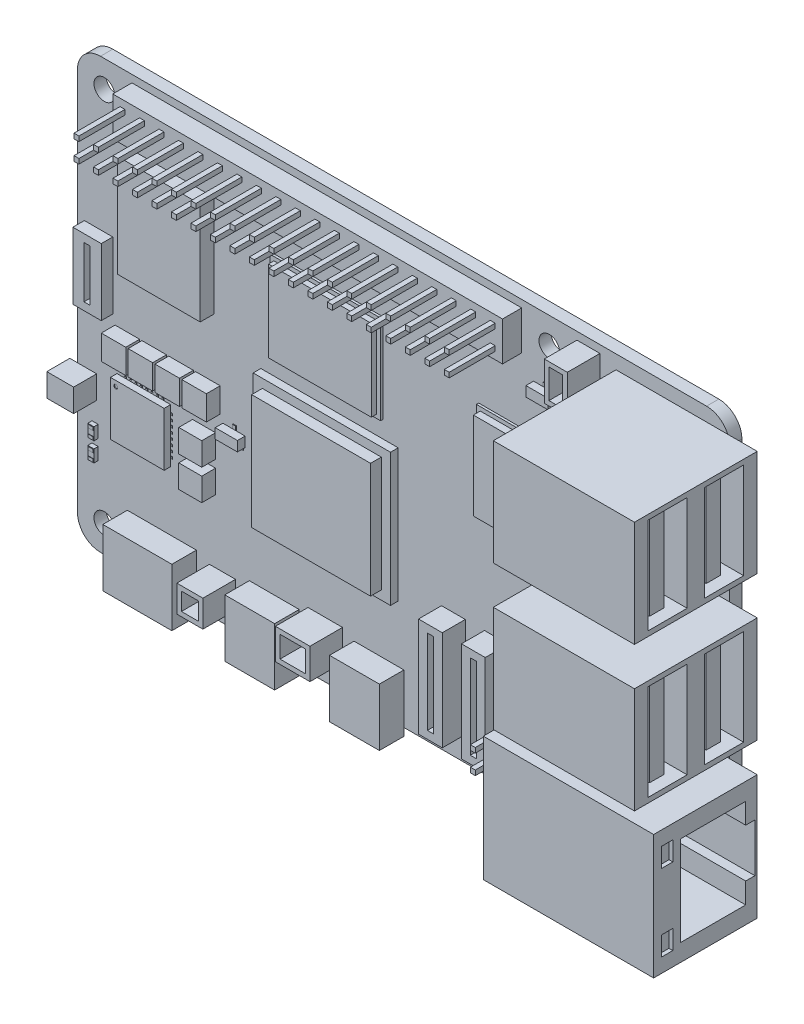
SolidWorks part; units mm, degrees
ref_plane "Front Plane" through (0, 0, 0) normal (0, 0, 1) x (1, 0, 0)
ref_plane "Top Plane" through (0, 0, 0) normal (0, 1, 0) x (1, 0, 0)
ref_plane "Right Plane" through (0, 0, 0) normal (1, 0, 0) x (0, 0, -1)
sketch "Sketch1" plane through (0, 0, 0) normal (0, 0, 1) x (1, 0, 0)
  line L0 (3, 0) -> (82, 0)
  line L1 (85, 3) -> (85, 53)
  line L2 (82, 56) -> (3, 56)
  line L3 (0, 53) -> (0, 3)
  arc A0 (82, 0) -> (85, 3) centre (82, 3) ccw
  arc A1 (85, 53) -> (82, 56) centre (82, 53) ccw
  arc A2 (3, 56) -> (0, 53) centre (3, 53) ccw
  arc A3 (0, 3) -> (3, 0) centre (3, 3) ccw
extrude "PCB" add sketch "Sketch1" along normal blind 1.6
ref_plane "Plane_z1_6" through (0, 0, 1.6) normal (0, 0, 1) x (1, 0, 0)
sketch "Sketch2" plane through (0, 0, 1.6) normal (0, 0, 1) x (1, 0, 0)
  line L1 (7.1, 49.96) -> (57.9, 49.96)
  line L2 (7.1, 49.96) -> (7.1, 55.04)
  line L3 (7.1, 55.04) -> (57.9, 55.04)
  line L4 (57.9, 49.96) -> (57.9, 55.04)
  line L6 (58.76, 6.76) -> (63.84, 6.76)
  line L7 (58.76, 6.76) -> (58.76, 11.84)
  line L8 (58.76, 11.84) -> (63.84, 11.84)
  line L9 (63.84, 6.76) -> (63.84, 11.84)
extrude "Header_Blocks" add sketch "Sketch2" along normal blind 2.5
ref_plane "Plane_z4_1" through (0, 0, 4.1) normal (0, 0, 1) x (1, 0, 0)
sketch "Sketch3" plane through (0, 0, 4.1) normal (0, 0, 1) x (1, 0, 0)
  line L1 (8.05, 50.91) -> (8.69, 50.91)
  line L2 (8.05, 50.91) -> (8.05, 51.55)
  line L3 (8.05, 51.55) -> (8.69, 51.55)
  line L4 (8.69, 50.91) -> (8.69, 51.55)
  line L6 (8.05, 53.45) -> (8.69, 53.45)
  line L7 (8.05, 53.45) -> (8.05, 54.09)
  line L8 (8.05, 54.09) -> (8.69, 54.09)
  line L9 (8.69, 53.45) -> (8.69, 54.09)
  line L11 (10.59, 50.91) -> (11.23, 50.91)
  line L12 (10.59, 50.91) -> (10.59, 51.55)
  line L13 (10.59, 51.55) -> (11.23, 51.55)
  line L14 (11.23, 50.91) -> (11.23, 51.55)
  line L16 (10.59, 53.45) -> (11.23, 53.45)
  line L17 (10.59, 53.45) -> (10.59, 54.09)
  line L18 (10.59, 54.09) -> (11.23, 54.09)
  line L19 (11.23, 53.45) -> (11.23, 54.09)
  line L21 (13.13, 50.91) -> (13.77, 50.91)
  line L22 (13.13, 50.91) -> (13.13, 51.55)
  line L23 (13.13, 51.55) -> (13.77, 51.55)
  line L24 (13.77, 50.91) -> (13.77, 51.55)
  line L26 (13.13, 53.45) -> (13.77, 53.45)
  line L27 (13.13, 53.45) -> (13.13, 54.09)
  line L28 (13.13, 54.09) -> (13.77, 54.09)
  line L29 (13.77, 53.45) -> (13.77, 54.09)
  line L31 (15.67, 50.91) -> (16.31, 50.91)
  line L32 (15.67, 50.91) -> (15.67, 51.55)
  line L33 (15.67, 51.55) -> (16.31, 51.55)
  line L34 (16.31, 50.91) -> (16.31, 51.55)
  line L36 (15.67, 53.45) -> (16.31, 53.45)
  line L37 (15.67, 53.45) -> (15.67, 54.09)
  line L38 (15.67, 54.09) -> (16.31, 54.09)
  line L39 (16.31, 53.45) -> (16.31, 54.09)
  line L41 (18.21, 50.91) -> (18.85, 50.91)
  line L42 (18.21, 50.91) -> (18.21, 51.55)
  line L43 (18.21, 51.55) -> (18.85, 51.55)
  line L44 (18.85, 50.91) -> (18.85, 51.55)
  line L46 (18.21, 53.45) -> (18.85, 53.45)
  line L47 (18.21, 53.45) -> (18.21, 54.09)
  line L48 (18.21, 54.09) -> (18.85, 54.09)
  line L49 (18.85, 53.45) -> (18.85, 54.09)
  line L51 (20.75, 50.91) -> (21.39, 50.91)
  line L52 (20.75, 50.91) -> (20.75, 51.55)
  line L53 (20.75, 51.55) -> (21.39, 51.55)
  line L54 (21.39, 50.91) -> (21.39, 51.55)
  line L56 (20.75, 53.45) -> (21.39, 53.45)
  line L57 (20.75, 53.45) -> (20.75, 54.09)
  line L58 (20.75, 54.09) -> (21.39, 54.09)
  line L59 (21.39, 53.45) -> (21.39, 54.09)
  line L61 (23.29, 50.91) -> (23.93, 50.91)
  line L62 (23.29, 50.91) -> (23.29, 51.55)
  line L63 (23.29, 51.55) -> (23.93, 51.55)
  line L64 (23.93, 50.91) -> (23.93, 51.55)
  line L66 (23.29, 53.45) -> (23.93, 53.45)
  line L67 (23.29, 53.45) -> (23.29, 54.09)
  line L68 (23.29, 54.09) -> (23.93, 54.09)
  line L69 (23.93, 53.45) -> (23.93, 54.09)
  line L71 (25.83, 50.91) -> (26.47, 50.91)
  line L72 (25.83, 50.91) -> (25.83, 51.55)
  line L73 (25.83, 51.55) -> (26.47, 51.55)
  line L74 (26.47, 50.91) -> (26.47, 51.55)
  line L76 (25.83, 53.45) -> (26.47, 53.45)
  line L77 (25.83, 53.45) -> (25.83, 54.09)
  line L78 (25.83, 54.09) -> (26.47, 54.09)
  line L79 (26.47, 53.45) -> (26.47, 54.09)
  line L81 (28.37, 50.91) -> (29.01, 50.91)
  line L82 (28.37, 50.91) -> (28.37, 51.55)
  line L83 (28.37, 51.55) -> (29.01, 51.55)
  line L84 (29.01, 50.91) -> (29.01, 51.55)
  line L86 (28.37, 53.45) -> (29.01, 53.45)
  line L87 (28.37, 53.45) -> (28.37, 54.09)
  line L88 (28.37, 54.09) -> (29.01, 54.09)
  line L89 (29.01, 53.45) -> (29.01, 54.09)
  line L91 (30.91, 50.91) -> (31.55, 50.91)
  line L92 (30.91, 50.91) -> (30.91, 51.55)
  line L93 (30.91, 51.55) -> (31.55, 51.55)
  line L94 (31.55, 50.91) -> (31.55, 51.55)
  line L96 (30.91, 53.45) -> (31.55, 53.45)
  line L97 (30.91, 53.45) -> (30.91, 54.09)
  line L98 (30.91, 54.09) -> (31.55, 54.09)
  line L99 (31.55, 53.45) -> (31.55, 54.09)
  line L101 (33.45, 50.91) -> (34.09, 50.91)
  line L102 (33.45, 50.91) -> (33.45, 51.55)
  line L103 (33.45, 51.55) -> (34.09, 51.55)
  line L104 (34.09, 50.91) -> (34.09, 51.55)
  line L106 (33.45, 53.45) -> (34.09, 53.45)
  line L107 (33.45, 53.45) -> (33.45, 54.09)
  line L108 (33.45, 54.09) -> (34.09, 54.09)
  line L109 (34.09, 53.45) -> (34.09, 54.09)
  line L111 (35.99, 50.91) -> (36.63, 50.91)
  line L112 (35.99, 50.91) -> (35.99, 51.55)
  line L113 (35.99, 51.55) -> (36.63, 51.55)
  line L114 (36.63, 50.91) -> (36.63, 51.55)
  line L116 (35.99, 53.45) -> (36.63, 53.45)
  line L117 (35.99, 53.45) -> (35.99, 54.09)
  line L118 (35.99, 54.09) -> (36.63, 54.09)
  line L119 (36.63, 53.45) -> (36.63, 54.09)
  line L121 (38.53, 50.91) -> (39.17, 50.91)
  line L122 (38.53, 50.91) -> (38.53, 51.55)
  line L123 (38.53, 51.55) -> (39.17, 51.55)
  line L124 (39.17, 50.91) -> (39.17, 51.55)
  line L126 (38.53, 53.45) -> (39.17, 53.45)
  line L127 (38.53, 53.45) -> (38.53, 54.09)
  line L128 (38.53, 54.09) -> (39.17, 54.09)
  line L129 (39.17, 53.45) -> (39.17, 54.09)
  line L131 (41.07, 50.91) -> (41.71, 50.91)
  line L132 (41.07, 50.91) -> (41.07, 51.55)
  line L133 (41.07, 51.55) -> (41.71, 51.55)
  line L134 (41.71, 50.91) -> (41.71, 51.55)
  line L136 (41.07, 53.45) -> (41.71, 53.45)
  line L137 (41.07, 53.45) -> (41.07, 54.09)
  line L138 (41.07, 54.09) -> (41.71, 54.09)
  line L139 (41.71, 53.45) -> (41.71, 54.09)
  line L141 (43.61, 50.91) -> (44.25, 50.91)
  line L142 (43.61, 50.91) -> (43.61, 51.55)
  line L143 (43.61, 51.55) -> (44.25, 51.55)
  line L144 (44.25, 50.91) -> (44.25, 51.55)
  line L146 (43.61, 53.45) -> (44.25, 53.45)
  line L147 (43.61, 53.45) -> (43.61, 54.09)
  line L148 (43.61, 54.09) -> (44.25, 54.09)
  line L149 (44.25, 53.45) -> (44.25, 54.09)
  line L151 (46.15, 50.91) -> (46.79, 50.91)
  line L152 (46.15, 50.91) -> (46.15, 51.55)
  line L153 (46.15, 51.55) -> (46.79, 51.55)
  line L154 (46.79, 50.91) -> (46.79, 51.55)
  line L156 (46.15, 53.45) -> (46.79, 53.45)
  line L157 (46.15, 53.45) -> (46.15, 54.09)
  line L158 (46.15, 54.09) -> (46.79, 54.09)
  line L159 (46.79, 53.45) -> (46.79, 54.09)
  line L161 (48.69, 50.91) -> (49.33, 50.91)
  line L162 (48.69, 50.91) -> (48.69, 51.55)
  line L163 (48.69, 51.55) -> (49.33, 51.55)
  line L164 (49.33, 50.91) -> (49.33, 51.55)
  line L166 (48.69, 53.45) -> (49.33, 53.45)
  line L167 (48.69, 53.45) -> (48.69, 54.09)
  line L168 (48.69, 54.09) -> (49.33, 54.09)
  line L169 (49.33, 53.45) -> (49.33, 54.09)
  line L171 (51.23, 50.91) -> (51.87, 50.91)
  line L172 (51.23, 50.91) -> (51.23, 51.55)
  line L173 (51.23, 51.55) -> (51.87, 51.55)
  line L174 (51.87, 50.91) -> (51.87, 51.55)
  line L176 (51.23, 53.45) -> (51.87, 53.45)
  line L177 (51.23, 53.45) -> (51.23, 54.09)
  line L178 (51.23, 54.09) -> (51.87, 54.09)
  line L179 (51.87, 53.45) -> (51.87, 54.09)
  line L181 (53.77, 50.91) -> (54.41, 50.91)
  line L182 (53.77, 50.91) -> (53.77, 51.55)
  line L183 (53.77, 51.55) -> (54.41, 51.55)
  line L184 (54.41, 50.91) -> (54.41, 51.55)
  line L186 (53.77, 53.45) -> (54.41, 53.45)
  line L187 (53.77, 53.45) -> (53.77, 54.09)
  line L188 (53.77, 54.09) -> (54.41, 54.09)
  line L189 (54.41, 53.45) -> (54.41, 54.09)
  line L191 (56.31, 50.91) -> (56.95, 50.91)
  line L192 (56.31, 50.91) -> (56.31, 51.55)
  line L193 (56.31, 51.55) -> (56.95, 51.55)
  line L194 (56.95, 50.91) -> (56.95, 51.55)
  line L196 (56.31, 53.45) -> (56.95, 53.45)
  line L197 (56.31, 53.45) -> (56.31, 54.09)
  line L198 (56.31, 54.09) -> (56.95, 54.09)
  line L199 (56.95, 53.45) -> (56.95, 54.09)
  line L201 (59.71, 7.71) -> (60.35, 7.71)
  line L202 (59.71, 7.71) -> (59.71, 8.35)
  line L203 (59.71, 8.35) -> (60.35, 8.35)
  line L204 (60.35, 7.71) -> (60.35, 8.35)
  line L206 (59.71, 10.25) -> (60.35, 10.25)
  line L207 (59.71, 10.25) -> (59.71, 10.89)
  line L208 (59.71, 10.89) -> (60.35, 10.89)
  line L209 (60.35, 10.25) -> (60.35, 10.89)
  line L211 (62.25, 7.71) -> (62.89, 7.71)
  line L212 (62.25, 7.71) -> (62.25, 8.35)
  line L213 (62.25, 8.35) -> (62.89, 8.35)
  line L214 (62.89, 7.71) -> (62.89, 8.35)
  line L216 (62.25, 10.25) -> (62.89, 10.25)
  line L217 (62.25, 10.25) -> (62.25, 10.89)
  line L218 (62.25, 10.89) -> (62.89, 10.89)
  line L219 (62.89, 10.25) -> (62.89, 10.89)
extrude "Header_Pins" add sketch "Sketch3" along normal blind 6
sketch "Sketch4" plane through (0, 0, 1.6) normal (0, 0, 1) x (1, 0, 0)
  line L1 (6.125, 14.1) -> (6.375, 14.1)
  line L2 (6.125, 14.1) -> (6.125, 14.4)
  line L3 (6.125, 14.4) -> (6.375, 14.4)
  line L4 (6.375, 14.1) -> (6.375, 14.4)
  line L6 (5, 15.225) -> (5.3, 15.225)
  line L7 (5, 15.225) -> (5, 15.475)
  line L8 (5, 15.475) -> (5.3, 15.475)
  line L9 (5.3, 15.225) -> (5.3, 15.475)
  line L11 (6.125, 21.2) -> (6.375, 21.2)
  line L12 (6.125, 21.2) -> (6.125, 21.5)
  line L13 (6.125, 21.5) -> (6.375, 21.5)
  line L14 (6.375, 21.2) -> (6.375, 21.5)
  line L16 (12.1, 15.225) -> (12.4, 15.225)
  line L17 (12.1, 15.225) -> (12.1, 15.475)
  line L18 (12.1, 15.475) -> (12.4, 15.475)
  line L19 (12.4, 15.225) -> (12.4, 15.475)
  line L21 (6.825, 14.1) -> (7.075, 14.1)
  line L22 (6.825, 14.1) -> (6.825, 14.4)
  line L23 (6.825, 14.4) -> (7.075, 14.4)
  line L24 (7.075, 14.1) -> (7.075, 14.4)
  line L26 (5, 15.925) -> (5.3, 15.925)
  line L27 (5, 15.925) -> (5, 16.175)
  line L28 (5, 16.175) -> (5.3, 16.175)
  line L29 (5.3, 15.925) -> (5.3, 16.175)
  line L31 (6.825, 21.2) -> (7.075, 21.2)
  line L32 (6.825, 21.2) -> (6.825, 21.5)
  line L33 (6.825, 21.5) -> (7.075, 21.5)
  line L34 (7.075, 21.2) -> (7.075, 21.5)
  line L36 (12.1, 15.925) -> (12.4, 15.925)
  line L37 (12.1, 15.925) -> (12.1, 16.175)
  line L38 (12.1, 16.175) -> (12.4, 16.175)
  line L39 (12.4, 15.925) -> (12.4, 16.175)
  line L41 (7.525, 14.1) -> (7.775, 14.1)
  line L42 (7.525, 14.1) -> (7.525, 14.4)
  line L43 (7.525, 14.4) -> (7.775, 14.4)
  line L44 (7.775, 14.1) -> (7.775, 14.4)
  line L46 (5, 16.625) -> (5.3, 16.625)
  line L47 (5, 16.625) -> (5, 16.875)
  line L48 (5, 16.875) -> (5.3, 16.875)
  line L49 (5.3, 16.625) -> (5.3, 16.875)
  line L51 (7.525, 21.2) -> (7.775, 21.2)
  line L52 (7.525, 21.2) -> (7.525, 21.5)
  line L53 (7.525, 21.5) -> (7.775, 21.5)
  line L54 (7.775, 21.2) -> (7.775, 21.5)
  line L56 (12.1, 16.625) -> (12.4, 16.625)
  line L57 (12.1, 16.625) -> (12.1, 16.875)
  line L58 (12.1, 16.875) -> (12.4, 16.875)
  line L59 (12.4, 16.625) -> (12.4, 16.875)
  line L61 (8.225, 14.1) -> (8.475, 14.1)
  line L62 (8.225, 14.1) -> (8.225, 14.4)
  line L63 (8.225, 14.4) -> (8.475, 14.4)
  line L64 (8.475, 14.1) -> (8.475, 14.4)
  line L66 (5, 17.325) -> (5.3, 17.325)
  line L67 (5, 17.325) -> (5, 17.575)
  line L68 (5, 17.575) -> (5.3, 17.575)
  line L69 (5.3, 17.325) -> (5.3, 17.575)
  line L71 (8.225, 21.2) -> (8.475, 21.2)
  line L72 (8.225, 21.2) -> (8.225, 21.5)
  line L73 (8.225, 21.5) -> (8.475, 21.5)
  line L74 (8.475, 21.2) -> (8.475, 21.5)
  line L76 (12.1, 17.325) -> (12.4, 17.325)
  line L77 (12.1, 17.325) -> (12.1, 17.575)
  line L78 (12.1, 17.575) -> (12.4, 17.575)
  line L79 (12.4, 17.325) -> (12.4, 17.575)
  line L81 (8.925, 14.1) -> (9.175, 14.1)
  line L82 (8.925, 14.1) -> (8.925, 14.4)
  line L83 (8.925, 14.4) -> (9.175, 14.4)
  line L84 (9.175, 14.1) -> (9.175, 14.4)
  line L86 (5, 18.025) -> (5.3, 18.025)
  line L87 (5, 18.025) -> (5, 18.275)
  line L88 (5, 18.275) -> (5.3, 18.275)
  line L89 (5.3, 18.025) -> (5.3, 18.275)
  line L91 (8.925, 21.2) -> (9.175, 21.2)
  line L92 (8.925, 21.2) -> (8.925, 21.5)
  line L93 (8.925, 21.5) -> (9.175, 21.5)
  line L94 (9.175, 21.2) -> (9.175, 21.5)
  line L96 (12.1, 18.025) -> (12.4, 18.025)
  line L97 (12.1, 18.025) -> (12.1, 18.275)
  line L98 (12.1, 18.275) -> (12.4, 18.275)
  line L99 (12.4, 18.025) -> (12.4, 18.275)
  line L101 (9.625, 14.1) -> (9.875, 14.1)
  line L102 (9.625, 14.1) -> (9.625, 14.4)
  line L103 (9.625, 14.4) -> (9.875, 14.4)
  line L104 (9.875, 14.1) -> (9.875, 14.4)
  line L106 (5, 18.725) -> (5.3, 18.725)
  line L107 (5, 18.725) -> (5, 18.975)
  line L108 (5, 18.975) -> (5.3, 18.975)
  line L109 (5.3, 18.725) -> (5.3, 18.975)
  line L111 (9.625, 21.2) -> (9.875, 21.2)
  line L112 (9.625, 21.2) -> (9.625, 21.5)
  line L113 (9.625, 21.5) -> (9.875, 21.5)
  line L114 (9.875, 21.2) -> (9.875, 21.5)
  line L116 (12.1, 18.725) -> (12.4, 18.725)
  line L117 (12.1, 18.725) -> (12.1, 18.975)
  line L118 (12.1, 18.975) -> (12.4, 18.975)
  line L119 (12.4, 18.725) -> (12.4, 18.975)
  line L121 (10.325, 14.1) -> (10.575, 14.1)
  line L122 (10.325, 14.1) -> (10.325, 14.35)
  line L123 (10.325, 14.35) -> (10.575, 14.35)
  line L124 (10.575, 14.1) -> (10.575, 14.35)
  line L126 (5, 19.425) -> (5.25, 19.425)
  line L127 (5, 19.425) -> (5, 19.675)
  line L128 (5, 19.675) -> (5.25, 19.675)
  line L129 (5.25, 19.425) -> (5.25, 19.675)
  line L131 (10.325, 21.2) -> (10.575, 21.2)
  line L132 (10.325, 21.2) -> (10.325, 21.5)
  line L133 (10.325, 21.5) -> (10.575, 21.5)
  line L134 (10.575, 21.2) -> (10.575, 21.5)
  line L136 (12.1, 19.425) -> (12.4, 19.425)
  line L137 (12.1, 19.425) -> (12.1, 19.675)
  line L138 (12.1, 19.675) -> (12.4, 19.675)
  line L139 (12.4, 19.425) -> (12.4, 19.675)
  line L141 (11.025, 14.1) -> (11.275, 14.1)
  line L142 (11.025, 14.1) -> (11.025, 14.4)
  line L143 (11.025, 14.4) -> (11.275, 14.4)
  line L144 (11.275, 14.1) -> (11.275, 14.4)
  line L146 (5, 20.125) -> (5.3, 20.125)
  line L147 (5, 20.125) -> (5, 20.375)
  line L148 (5, 20.375) -> (5.3, 20.375)
  line L149 (5.3, 20.125) -> (5.3, 20.375)
  line L151 (11.025, 21.2) -> (11.275, 21.2)
  line L152 (11.025, 21.2) -> (11.025, 21.5)
  line L153 (11.025, 21.5) -> (11.275, 21.5)
  line L154 (11.275, 21.2) -> (11.275, 21.5)
  line L156 (12.1, 20.125) -> (12.4, 20.125)
  line L157 (12.1, 20.125) -> (12.1, 20.375)
  line L158 (12.1, 20.375) -> (12.4, 20.375)
  line L159 (12.4, 20.125) -> (12.4, 20.375)
  line L161 (66.275, 43.15) -> (66.525, 43.15)
  line L162 (66.275, 43.15) -> (66.275, 43.45)
  line L163 (66.275, 43.45) -> (66.525, 43.45)
  line L164 (66.525, 43.15) -> (66.525, 43.45)
  line L166 (65.2, 44.475) -> (65.5, 44.475)
  line L167 (65.2, 44.475) -> (65.2, 44.725)
  line L168 (65.2, 44.725) -> (65.5, 44.725)
  line L169 (65.5, 44.475) -> (65.5, 44.725)
  line L171 (66.275, 47.75) -> (66.525, 47.75)
  line L172 (66.275, 47.75) -> (66.275, 48.05)
  line L173 (66.275, 48.05) -> (66.525, 48.05)
  line L174 (66.525, 47.75) -> (66.525, 48.05)
  line L176 (69.3, 44.475) -> (69.6, 44.475)
  line L177 (69.3, 44.475) -> (69.3, 44.725)
  line L178 (69.3, 44.725) -> (69.6, 44.725)
  line L179 (69.6, 44.475) -> (69.6, 44.725)
  line L181 (66.9417, 43.15) -> (67.1917, 43.15)
  line L182 (66.9417, 43.15) -> (66.9417, 43.45)
  line L183 (66.9417, 43.45) -> (67.1917, 43.45)
  line L184 (67.1917, 43.15) -> (67.1917, 43.45)
  line L186 (65.2, 45.1417) -> (65.5, 45.1417)
  line L187 (65.2, 45.1417) -> (65.2, 45.3917)
  line L188 (65.2, 45.3917) -> (65.5, 45.3917)
  line L189 (65.5, 45.1417) -> (65.5, 45.3917)
  line L191 (66.9417, 47.75) -> (67.1917, 47.75)
  line L192 (66.9417, 47.75) -> (66.9417, 48.05)
  line L193 (66.9417, 48.05) -> (67.1917, 48.05)
  line L194 (67.1917, 47.75) -> (67.1917, 48.05)
  line L196 (69.3, 45.1417) -> (69.6, 45.1417)
  line L197 (69.3, 45.1417) -> (69.3, 45.3917)
  line L198 (69.3, 45.3917) -> (69.6, 45.3917)
  line L199 (69.6, 45.1417) -> (69.6, 45.3917)
  line L201 (67.6083, 43.15) -> (67.8583, 43.15)
  line L202 (67.6083, 43.15) -> (67.6083, 43.45)
  line L203 (67.6083, 43.45) -> (67.8583, 43.45)
  line L204 (67.8583, 43.15) -> (67.8583, 43.45)
  line L206 (65.2, 45.8083) -> (65.5, 45.8083)
  line L207 (65.2, 45.8083) -> (65.2, 46.0583)
  line L208 (65.2, 46.0583) -> (65.5, 46.0583)
  line L209 (65.5, 45.8083) -> (65.5, 46.0583)
  line L211 (67.6083, 47.75) -> (67.8583, 47.75)
  line L212 (67.6083, 47.75) -> (67.6083, 48.05)
  line L213 (67.6083, 48.05) -> (67.8583, 48.05)
  line L214 (67.8583, 47.75) -> (67.8583, 48.05)
  line L216 (69.3, 45.8083) -> (69.6, 45.8083)
  line L217 (69.3, 45.8083) -> (69.3, 46.0583)
  line L218 (69.3, 46.0583) -> (69.6, 46.0583)
  line L219 (69.6, 45.8083) -> (69.6, 46.0583)
  line L221 (68.275, 43.15) -> (68.525, 43.15)
  line L222 (68.275, 43.15) -> (68.275, 43.45)
  line L223 (68.275, 43.45) -> (68.525, 43.45)
  line L224 (68.525, 43.15) -> (68.525, 43.45)
  line L226 (65.2, 46.475) -> (65.5, 46.475)
  line L227 (65.2, 46.475) -> (65.2, 46.725)
  line L228 (65.2, 46.725) -> (65.5, 46.725)
  line L229 (65.5, 46.475) -> (65.5, 46.725)
  line L231 (68.275, 47.75) -> (68.525, 47.75)
  line L232 (68.275, 47.75) -> (68.275, 48.05)
  line L233 (68.275, 48.05) -> (68.525, 48.05)
  line L234 (68.525, 47.75) -> (68.525, 48.05)
  line L236 (69.3, 46.475) -> (69.6, 46.475)
  line L237 (69.3, 46.475) -> (69.3, 46.725)
  line L238 (69.3, 46.725) -> (69.6, 46.725)
  line L239 (69.6, 46.475) -> (69.6, 46.725)
extrude "Parts_add00" add sketch "Sketch4" along normal blind 0.05
sketch "Sketch5" plane through (0, 0, 1.6) normal (0, 0, 1) x (1, 0, 0)
  line L1 (19.35, 20.85) -> (19.75, 20.85)
  line L2 (19.35, 20.85) -> (19.35, 21.55)
  line L3 (19.35, 21.55) -> (19.75, 21.55)
  line L4 (19.75, 20.85) -> (19.75, 21.55)
  line L6 (21.25, 20.85) -> (21.65, 20.85)
  line L7 (21.25, 20.85) -> (21.25, 21.55)
  line L8 (21.25, 21.55) -> (21.65, 21.55)
  line L9 (21.65, 20.85) -> (21.65, 21.55)
  line L11 (20.3, 22.45) -> (20.7, 22.45)
  line L12 (20.3, 22.45) -> (20.3, 23.15)
  line L13 (20.3, 23.15) -> (20.7, 23.15)
  line L14 (20.7, 22.45) -> (20.7, 23.15)
  line L16 (58.35, 16.85) -> (58.75, 16.85)
  line L17 (58.35, 16.85) -> (58.35, 17.55)
  line L18 (58.35, 17.55) -> (58.75, 17.55)
  line L19 (58.75, 16.85) -> (58.75, 17.55)
  line L21 (60.25, 16.85) -> (60.65, 16.85)
  line L22 (60.25, 16.85) -> (60.25, 17.55)
  line L23 (60.25, 17.55) -> (60.65, 17.55)
  line L24 (60.65, 16.85) -> (60.65, 17.55)
  line L26 (59.3, 18.45) -> (59.7, 18.45)
  line L27 (59.3, 18.45) -> (59.3, 19.15)
  line L28 (59.3, 19.15) -> (59.7, 19.15)
  line L29 (59.7, 18.45) -> (59.7, 19.15)
  line L31 (59.85, 45.85) -> (60.25, 45.85)
  line L32 (59.85, 45.85) -> (59.85, 46.55)
  line L33 (59.85, 46.55) -> (60.25, 46.55)
  line L34 (60.25, 45.85) -> (60.25, 46.55)
  line L36 (61.75, 45.85) -> (62.15, 45.85)
  line L37 (61.75, 45.85) -> (61.75, 46.55)
  line L38 (61.75, 46.55) -> (62.15, 46.55)
  line L39 (62.15, 45.85) -> (62.15, 46.55)
  line L41 (60.8, 47.45) -> (61.2, 47.45)
  line L42 (60.8, 47.45) -> (60.8, 48.15)
  line L43 (60.8, 48.15) -> (61.2, 48.15)
  line L44 (61.2, 47.45) -> (61.2, 48.15)
extrude "Parts_add01" add sketch "Sketch5" along normal blind 0.1
sketch "Sketch6" plane through (0, 0, 1.6) normal (0, 0, 1) x (1, 0, 0)
  line L1 (25.4, 33.4) -> (39.8, 33.4)
  line L2 (25.4, 33.4) -> (25.4, 45)
  line L3 (25.4, 45) -> (39.8, 45)
  line L4 (39.8, 33.4) -> (39.8, 45)
  line L6 (52.3, 29.1) -> (65.2, 29.1)
  line L7 (52.3, 29.1) -> (52.3, 41.5)
  line L8 (52.3, 41.5) -> (65.2, 41.5)
  line L9 (65.2, 29.1) -> (65.2, 41.5)
extrude "Parts_add02" add sketch "Sketch6" along normal blind 0.3
sketch "Sketch7" plane through (0, 0, 1.6) normal (0, 0, 1) x (1, 0, 0)
  line L1 (1.9, 10.2) -> (2.7, 10.2)
  line L2 (1.9, 10.2) -> (1.9, 11.8)
  line L3 (1.9, 11.8) -> (2.7, 11.8)
  line L4 (2.7, 10.2) -> (2.7, 11.8)
  line L6 (1.9, 12.7) -> (2.7, 12.7)
  line L7 (1.9, 12.7) -> (1.9, 14.3)
  line L8 (1.9, 14.3) -> (2.7, 14.3)
  line L9 (2.7, 12.7) -> (2.7, 14.3)
extrude "Parts_add03" add sketch "Sketch7" along normal blind 0.55
sketch "Sketch8" plane through (0, 0, 1.6) normal (0, 0, 1) x (1, 0, 0)
  line L0 (62.7, 19.918) -> (65.882, 23.1)
  line L1 (65.882, 23.1) -> (62.7, 26.282)
  line L2 (62.7, 26.282) -> (59.518, 23.1)
  line L3 (59.518, 23.1) -> (62.7, 19.918)
extrude "Parts_add04" add sketch "Sketch8" along normal blind 0.9
sketch "Sketch9" plane through (0, 0, 1.6) normal (0, 0, 1) x (1, 0, 0)
  line L1 (23.9, 13.9) -> (41.8, 13.9)
  line L2 (23.9, 13.9) -> (23.9, 31.2)
  line L3 (23.9, 31.2) -> (41.8, 31.2)
  line L4 (41.8, 13.9) -> (41.8, 31.2)
extrude "Parts_add05" add sketch "Sketch9" along normal blind 1
sketch "Sketch10" plane through (0, 0, 1.6) normal (0, 0, 1) x (1, 0, 0)
  line L1 (0.9, 27.7) -> (4.6, 27.7)
  line L2 (0.9, 27.7) -> (0.9, 36.4)
  line L3 (0.9, 36.4) -> (4.6, 36.4)
  line L4 (4.6, 27.7) -> (4.6, 36.4)
extrude "Parts_add06" add sketch "Sketch10" along normal blind 1.5
sketch "Sketch11" plane through (0, 0, 1.6) normal (0, 0, 1) x (1, 0, 0)
  line L1 (7, 34.3) -> (17.8, 34.3)
  line L2 (7, 34.3) -> (7, 47.6)
  line L3 (7, 47.6) -> (17.8, 47.6)
  line L4 (17.8, 34.3) -> (17.8, 47.6)
  line L6 (4.9, 23.4) -> (8.1, 23.4)
  line L7 (4.9, 23.4) -> (4.9, 26.6)
  line L8 (4.9, 26.6) -> (8.1, 26.6)
  line L9 (8.1, 23.4) -> (8.1, 26.6)
  line L11 (8.4, 23.4) -> (11.6, 23.4)
  line L12 (8.4, 23.4) -> (8.4, 26.6)
  line L13 (8.4, 26.6) -> (11.6, 26.6)
  line L14 (11.6, 23.4) -> (11.6, 26.6)
  line L16 (11.9, 23.4) -> (15.1, 23.4)
  line L17 (11.9, 23.4) -> (11.9, 26.6)
  line L18 (11.9, 26.6) -> (15.1, 26.6)
  line L19 (15.1, 23.4) -> (15.1, 26.6)
  line L21 (15.4, 23.4) -> (18.6, 23.4)
  line L22 (15.4, 23.4) -> (15.4, 26.6)
  line L23 (15.4, 26.6) -> (18.6, 26.6)
  line L24 (18.6, 23.4) -> (18.6, 26.6)
  line L26 (15, 18) -> (18, 18)
  line L27 (15, 18) -> (15, 21)
  line L28 (15, 21) -> (18, 21)
  line L29 (18, 18) -> (18, 21)
  line L31 (15, 14) -> (18, 14)
  line L32 (15, 14) -> (15, 17)
  line L33 (15, 17) -> (18, 17)
  line L34 (18, 14) -> (18, 17)
extrude "Parts_add07" add sketch "Sketch11" along normal blind 1.8
sketch "Sketch12" plane through (0, 0, 1.6) normal (0, 0, 1) x (1, 0, 0)
  line L1 (53.05, 3.2) -> (56.15, 3.2)
  line L2 (53.05, 3.2) -> (53.05, 16.2)
  line L3 (53.05, 16.2) -> (56.15, 16.2)
  line L4 (56.15, 3.2) -> (56.15, 16.2)
  line L6 (47.45, 3.2) -> (50.55, 3.2)
  line L7 (47.45, 3.2) -> (47.45, 16.2)
  line L8 (47.45, 16.2) -> (50.55, 16.2)
  line L9 (50.55, 3.2) -> (50.55, 16.2)
  line L11 (-1, 16.9) -> (2.5, 16.9)
  line L12 (-1, 16.9) -> (-1, 19.9)
  line L13 (-1, 19.9) -> (2.5, 19.9)
  line L14 (2.5, 16.9) -> (2.5, 19.9)
extrude "Parts_add08" add sketch "Sketch12" along normal blind 3
sketch "Sketch13" plane through (0, 0, 1.6) normal (0, 0, 1) x (1, 0, 0)
  line L1 (22.4, -1) -> (28.9, -1)
  line L2 (22.4, -1) -> (22.4, 6.5)
  line L3 (22.4, 6.5) -> (28.9, 6.5)
  line L4 (28.9, -1) -> (28.9, 6.5)
  line L6 (36.05, -1) -> (42.55, -1)
  line L7 (36.05, -1) -> (36.05, 6.5)
  line L8 (36.05, 6.5) -> (42.55, 6.5)
  line L9 (42.55, -1) -> (42.55, 6.5)
  line L11 (6.5, -1) -> (15.5, -1)
  line L12 (6.5, -1) -> (6.5, 6.5)
  line L13 (6.5, 6.5) -> (15.5, 6.5)
  line L14 (15.5, -1) -> (15.5, 6.5)
extrude "Parts_add09" add sketch "Sketch13" along normal blind 3.2
sketch "Sketch14" plane through (0, 0, 1.6) normal (0, 0, 1) x (1, 0, 0)
  line L1 (65.1, 50) -> (68.1, 50)
  line L2 (65.1, 50) -> (65.1, 55)
  line L3 (65.1, 55) -> (68.1, 55)
  line L4 (68.1, 50) -> (68.1, 55)
  line L6 (30.05, 3.3) -> (34.55, 3.3)
  line L7 (30.05, 3.3) -> (30.05, 7.3)
  line L8 (30.05, 7.3) -> (34.55, 7.3)
  line L9 (34.55, 3.3) -> (34.55, 7.3)
  line L11 (17.2, 2.25) -> (20.6, 2.25)
  line L12 (17.2, 2.25) -> (17.2, 5.75)
  line L13 (17.2, 5.75) -> (20.6, 5.75)
  line L14 (20.6, 2.25) -> (20.6, 5.75)
extrude "Parts_add10" add sketch "Sketch14" along normal blind 4.25
sketch "Sketch15" plane through (0, 0, 1.6) normal (0, 0, 1) x (1, 0, 0)
  line L1 (66.4, 1.5) -> (88.6, 1.5)
  line L2 (66.4, 1.5) -> (66.4, 17.7)
  line L3 (66.4, 17.7) -> (88.6, 17.7)
  line L4 (88.6, 1.5) -> (88.6, 17.7)
extrude "Parts_add11" add sketch "Sketch15" along normal blind 13.5
sketch "Sketch16" plane through (0, 0, 1.6) normal (0, 0, 1) x (1, 0, 0)
  line L1 (70.2, 40.4) -> (88.6, 40.4)
  line L2 (70.2, 40.4) -> (70.2, 54.2)
  line L3 (70.2, 54.2) -> (88.6, 54.2)
  line L4 (88.6, 40.4) -> (88.6, 54.2)
  line L6 (70.2, 21.6) -> (88.6, 21.6)
  line L7 (70.2, 21.6) -> (70.2, 35.4)
  line L8 (70.2, 35.4) -> (88.6, 35.4)
  line L9 (88.6, 21.6) -> (88.6, 35.4)
extrude "Parts_add12" add sketch "Sketch16" along normal blind 16
ref_plane "Plane_z1_65" through (0, 0, 1.65) normal (0, 0, 1) x (1, 0, 0)
sketch "Sketch17" plane through (0, 0, 1.65) normal (0, 0, 1) x (1, 0, 0)
  line L1 (5.2, 14.3) -> (12.2, 14.3)
  line L2 (5.2, 14.3) -> (5.2, 21.3)
  line L3 (5.2, 21.3) -> (12.2, 21.3)
  line L4 (12.2, 14.3) -> (12.2, 21.3)
extrude "Parts_add13" add sketch "Sketch17" along normal blind 0.85
sketch "Sketch18" plane through (0, 0, 1.65) normal (0, 0, 1) x (1, 0, 0)
  line L1 (65.4, 43.35) -> (69.4, 43.35)
  line L2 (65.4, 43.35) -> (65.4, 47.85)
  line L3 (65.4, 47.85) -> (69.4, 47.85)
  line L4 (69.4, 43.35) -> (69.4, 47.85)
extrude "Parts_add14" add sketch "Sketch18" along normal blind 0.95
ref_plane "Plane_z1_7" through (0, 0, 1.7) normal (0, 0, 1) x (1, 0, 0)
sketch "Sketch19" plane through (0, 0, 1.7) normal (0, 0, 1) x (1, 0, 0)
  line L1 (19.05, 21.35) -> (21.95, 21.35)
  line L2 (19.05, 21.35) -> (19.05, 22.65)
  line L3 (19.05, 22.65) -> (21.95, 22.65)
  line L4 (21.95, 21.35) -> (21.95, 22.65)
  line L6 (58.05, 17.35) -> (60.95, 17.35)
  line L7 (58.05, 17.35) -> (58.05, 18.65)
  line L8 (58.05, 18.65) -> (60.95, 18.65)
  line L9 (60.95, 17.35) -> (60.95, 18.65)
  line L11 (59.55, 46.35) -> (62.45, 46.35)
  line L12 (59.55, 46.35) -> (59.55, 47.65)
  line L13 (59.55, 47.65) -> (62.45, 47.65)
  line L14 (62.45, 46.35) -> (62.45, 47.65)
extrude "Parts_add15" add sketch "Sketch19" along normal blind 1
ref_plane "Plane_z1_9" through (0, 0, 1.9) normal (0, 0, 1) x (1, 0, 0)
sketch "Sketch20" plane through (0, 0, 1.9) normal (0, 0, 1) x (1, 0, 0)
  line L1 (25.9, 33.9) -> (39.3, 33.9)
  line L2 (25.9, 33.9) -> (25.9, 44.5)
  line L3 (25.9, 44.5) -> (39.3, 44.5)
  line L4 (39.3, 33.9) -> (39.3, 44.5)
extrude "Parts_add16" add sketch "Sketch20" along normal blind 0.7
sketch "Sketch21" plane through (0, 0, 1.9) normal (0, 0, 1) x (1, 0, 0)
  line L1 (52.8, 29.6) -> (64.7, 29.6)
  line L2 (52.8, 29.6) -> (52.8, 41)
  line L3 (52.8, 41) -> (64.7, 41)
  line L4 (64.7, 29.6) -> (64.7, 41)
extrude "Parts_add17" add sketch "Sketch21" along normal blind 0.9
ref_plane "Plane_z2_15" through (0, 0, 2.15) normal (0, 0, 1) x (1, 0, 0)
sketch "Sketch22" plane through (0, 0, 2.15) normal (0, 0, 1) x (1, 0, 0)
  line L1 (1.95, 10.25) -> (2.65, 10.25)
  line L2 (1.95, 10.25) -> (1.95, 10.65)
  line L3 (1.95, 10.65) -> (2.65, 10.65)
  line L4 (2.65, 10.25) -> (2.65, 10.65)
  line L6 (1.95, 11.35) -> (2.65, 11.35)
  line L7 (1.95, 11.35) -> (1.95, 11.75)
  line L8 (1.95, 11.75) -> (2.65, 11.75)
  line L9 (2.65, 11.35) -> (2.65, 11.75)
  line L11 (1.95, 12.75) -> (2.65, 12.75)
  line L12 (1.95, 12.75) -> (1.95, 13.15)
  line L13 (1.95, 13.15) -> (2.65, 13.15)
  line L14 (2.65, 12.75) -> (2.65, 13.15)
  line L16 (1.95, 13.85) -> (2.65, 13.85)
  line L17 (1.95, 13.85) -> (1.95, 14.25)
  line L18 (1.95, 14.25) -> (2.65, 14.25)
  line L19 (2.65, 13.85) -> (2.65, 14.25)
extrude "Parts_add18" add sketch "Sketch22" along normal blind 0.05
ref_plane "Plane_z2_6" through (0, 0, 2.6) normal (0, 0, 1) x (1, 0, 0)
sketch "Sketch23" plane through (0, 0, 2.6) normal (0, 0, 1) x (1, 0, 0)
  line L1 (25.1, 15.05) -> (40.6, 15.05)
  line L2 (25.1, 15.05) -> (25.1, 30.05)
  line L3 (25.1, 30.05) -> (40.6, 30.05)
  line L4 (40.6, 15.05) -> (40.6, 30.05)
extrude "Parts_add19" add sketch "Sketch23" along normal blind 1.4
ref_plane "Plane_x88_6" through (88.6, 0, 0) normal (1, 0, 0) x (0, 0, -1)
sketch "Sketch24" plane through (88.6, 0, 0) normal (1, 0, 0) x (0, 0, -1)
  line L1 (-12.6, 3.35) -> (-14.1, 3.35)
  line L2 (-12.6, 3.35) -> (-12.6, 5.85)
  line L3 (-12.6, 5.85) -> (-14.1, 5.85)
  line L4 (-14.1, 3.35) -> (-14.1, 5.85)
  line L6 (-12.6, 13.35) -> (-14.1, 13.35)
  line L7 (-12.6, 13.35) -> (-12.6, 15.85)
  line L8 (-12.6, 15.85) -> (-14.1, 15.85)
  line L9 (-14.1, 13.35) -> (-14.1, 15.85)
extrude "Parts_cut00" cut sketch "Sketch24" against normal blind 0.5
sketch "Sketch25" plane through (88.6, 0, 0) normal (1, 0, 0) x (0, 0, -1)
  line L1 (-5.57, 41.8) -> (-7.47, 41.8)
  line L2 (-5.57, 41.8) -> (-5.57, 52.8)
  line L3 (-5.57, 52.8) -> (-7.47, 52.8)
  line L4 (-7.47, 41.8) -> (-7.47, 52.8)
  line L6 (-12.93, 41.8) -> (-14.83, 41.8)
  line L7 (-12.93, 41.8) -> (-12.93, 52.8)
  line L8 (-12.93, 52.8) -> (-14.83, 52.8)
  line L9 (-14.83, 41.8) -> (-14.83, 52.8)
  line L11 (-5.57, 23) -> (-7.47, 23)
  line L12 (-5.57, 23) -> (-5.57, 34)
  line L13 (-5.57, 34) -> (-7.47, 34)
  line L14 (-7.47, 23) -> (-7.47, 34)
  line L16 (-12.93, 23) -> (-14.83, 23)
  line L17 (-12.93, 23) -> (-12.93, 34)
  line L18 (-12.93, 34) -> (-14.83, 34)
  line L19 (-14.83, 23) -> (-14.83, 34)
extrude "Parts_cut01" cut sketch "Sketch25" against normal blind 0.8
sketch "Sketch26" plane through (88.6, 0, 0) normal (1, 0, 0) x (0, 0, -1)
  line L1 (-3.37, 41.05) -> (-8.47, 41.05)
  line L2 (-3.37, 41.05) -> (-3.37, 53.55)
  line L3 (-3.37, 53.55) -> (-8.47, 53.55)
  line L4 (-8.47, 41.05) -> (-8.47, 53.55)
  line L6 (-5.57, 41.8) -> (-7.47, 41.8)
  line L7 (-5.57, 41.8) -> (-5.57, 52.8)
  line L8 (-5.57, 52.8) -> (-7.47, 52.8)
  line L9 (-7.47, 41.8) -> (-7.47, 52.8)
  line L11 (-10.73, 41.05) -> (-15.83, 41.05)
  line L12 (-10.73, 41.05) -> (-10.73, 53.55)
  line L13 (-10.73, 53.55) -> (-15.83, 53.55)
  line L14 (-15.83, 41.05) -> (-15.83, 53.55)
  line L16 (-12.93, 41.8) -> (-14.83, 41.8)
  line L17 (-12.93, 41.8) -> (-12.93, 52.8)
  line L18 (-12.93, 52.8) -> (-14.83, 52.8)
  line L19 (-14.83, 41.8) -> (-14.83, 52.8)
  line L21 (-3.37, 22.25) -> (-8.47, 22.25)
  line L22 (-3.37, 22.25) -> (-3.37, 34.75)
  line L23 (-3.37, 34.75) -> (-8.47, 34.75)
  line L24 (-8.47, 22.25) -> (-8.47, 34.75)
  line L26 (-5.57, 23) -> (-7.47, 23)
  line L27 (-5.57, 23) -> (-5.57, 34)
  line L28 (-5.57, 34) -> (-7.47, 34)
  line L29 (-7.47, 23) -> (-7.47, 34)
  line L31 (-10.73, 22.25) -> (-15.83, 22.25)
  line L32 (-10.73, 22.25) -> (-10.73, 34.75)
  line L33 (-10.73, 34.75) -> (-15.83, 34.75)
  line L34 (-15.83, 22.25) -> (-15.83, 34.75)
  line L36 (-12.93, 23) -> (-14.83, 23)
  line L37 (-12.93, 23) -> (-12.93, 34)
  line L38 (-12.93, 34) -> (-14.83, 34)
  line L39 (-14.83, 23) -> (-14.83, 34)
extrude "Parts_cut02" cut sketch "Sketch26" against normal blind 14
sketch "Sketch27" plane through (88.6, 0, 0) normal (1, 0, 0) x (0, 0, -1)
  line L0 (-3.1, 3.75) -> (-3.1, 6.45)
  line L1 (-3.1, 6.45) -> (-1.9, 6.45)
  line L2 (-1.9, 6.45) -> (-1.9, 12.75)
  line L3 (-1.9, 12.75) -> (-3.1, 12.75)
  line L4 (-3.1, 12.75) -> (-3.1, 15.45)
  line L5 (-3.1, 15.45) -> (-11.6, 15.45)
  line L6 (-11.6, 15.45) -> (-11.6, 3.75)
  line L7 (-11.6, 3.75) -> (-3.1, 3.75)
extrude "Parts_cut03" cut sketch "Sketch27" against normal blind 18
ref_plane "Plane_ym1" through (0, -1, 0) normal (0, 1, 0) x (1, 0, 0)
sketch "Sketch28" plane through (0, -1, 0) normal (0, 1, 0) x (1, 0, 0)
  line L1 (23.55, -2.9) -> (27.75, -2.9)
  line L2 (23.55, -2.9) -> (23.55, -3.5)
  line L3 (23.55, -3.5) -> (27.75, -3.5)
  line L4 (27.75, -2.9) -> (27.75, -3.5)
  line L6 (37.2, -2.9) -> (41.4, -2.9)
  line L7 (37.2, -2.9) -> (37.2, -3.5)
  line L8 (37.2, -3.5) -> (41.4, -3.5)
  line L9 (41.4, -2.9) -> (41.4, -3.5)
  line L11 (7.7, -2.85) -> (14.3, -2.85)
  line L12 (7.7, -2.85) -> (7.7, -3.55)
  line L13 (7.7, -3.55) -> (14.3, -3.55)
  line L14 (14.3, -2.85) -> (14.3, -3.55)
extrude "Parts_cut04" cut sketch "Sketch28" along normal blind 0.5
ref_plane "Plane_y6" through (0, 6, 0) normal (0, 1, 0) x (1, 0, 0)
sketch "Sketch29" plane through (0, 6, 0) normal (0, 1, 0) x (1, 0, 0)
  line L0 (8.1, -3.5) -> (13.9, -3.5) construction
  line L1 (22.9, -2.2) -> (28.4, -2.2)
  line L2 (22.9, -2.2) -> (22.9, -4.2)
  line L3 (22.9, -4.2) -> (28.4, -4.2)
  line L4 (28.4, -2.2) -> (28.4, -4.2)
  line L5 (8.1, -2.25) -> (13.9, -2.25)
  line L6 (23.55, -2.9) -> (27.75, -2.9)
  line L7 (23.55, -2.9) -> (23.55, -3.5)
  line L8 (23.55, -3.5) -> (27.75, -3.5)
  line L9 (27.75, -2.9) -> (27.75, -3.5)
  line L10 (8.1, -4.75) -> (13.9, -4.75)
  line L11 (36.55, -2.2) -> (42.05, -2.2)
  line L12 (36.55, -2.2) -> (36.55, -4.2)
  line L13 (36.55, -4.2) -> (42.05, -4.2)
  line L14 (42.05, -2.2) -> (42.05, -4.2)
  line L16 (37.2, -2.9) -> (41.4, -2.9)
  line L17 (37.2, -2.9) -> (37.2, -3.5)
  line L18 (37.2, -3.5) -> (41.4, -3.5)
  line L19 (41.4, -2.9) -> (41.4, -3.5)
  line L21 (7.7, -2.85) -> (14.3, -2.85)
  line L22 (7.7, -2.85) -> (7.7, -3.55)
  line L23 (7.7, -3.55) -> (14.3, -3.55)
  line L24 (14.3, -2.85) -> (14.3, -3.55)
  arc A0 (8.1, -2.25) -> (8.1, -4.75) centre (8.1, -3.5) ccw
  arc A1 (13.9, -4.75) -> (13.9, -2.25) centre (13.9, -3.5) ccw
  point P4 (11, -3.5)
extrude "Parts_cut05" cut sketch "Sketch29" against normal blind 7
ref_plane "Plane_z2_5" through (0, 0, 2.5) normal (0, 0, 1) x (1, 0, 0)
sketch "Sketch30" plane through (0, 0, 2.5) normal (0, 0, 1) x (1, 0, 0)
  circle A0 centre (5.9, 20.6) radius 0.25
extrude "Parts_cut06" cut sketch "Sketch30" against normal blind 0.1
sketch "Sketch31" plane through (0, 0, 2.6) normal (0, 0, 1) x (1, 0, 0)
  circle A0 centre (66.1, 47.15) radius 0.25
extrude "Parts_cut07" cut sketch "Sketch31" against normal blind 0.1
ref_plane "Plane_z3_1" through (0, 0, 3.1) normal (0, 0, 1) x (1, 0, 0)
sketch "Sketch32" plane through (0, 0, 3.1) normal (0, 0, 1) x (1, 0, 0)
  line L1 (2.35, 28.7) -> (3.15, 28.7)
  line L2 (2.35, 28.7) -> (2.35, 35.4)
  line L3 (2.35, 35.4) -> (3.15, 35.4)
  line L4 (3.15, 28.7) -> (3.15, 35.4)
extrude "Parts_cut08" cut sketch "Sketch32" against normal blind 1
ref_plane "Plane_z4_6" through (0, 0, 4.6) normal (0, 0, 1) x (1, 0, 0)
sketch "Sketch33" plane through (0, 0, 4.6) normal (0, 0, 1) x (1, 0, 0)
  line L1 (54.2, 4.2) -> (55, 4.2)
  line L2 (54.2, 4.2) -> (54.2, 15.2)
  line L3 (54.2, 15.2) -> (55, 15.2)
  line L4 (55, 4.2) -> (55, 15.2)
  line L6 (48.6, 4.2) -> (49.4, 4.2)
  line L7 (48.6, 4.2) -> (48.6, 15.2)
  line L8 (48.6, 15.2) -> (49.4, 15.2)
  line L9 (49.4, 4.2) -> (49.4, 15.2)
extrude "Parts_cut09" cut sketch "Sketch33" against normal blind 2.5
ref_plane "Plane_z5_85" through (0, 0, 5.85) normal (0, 0, 1) x (1, 0, 0)
sketch "Sketch34" plane through (0, 0, 5.85) normal (0, 0, 1) x (1, 0, 0)
  line L1 (65.7, 50.6) -> (67.5, 50.6)
  line L2 (65.7, 50.6) -> (65.7, 54.4)
  line L3 (65.7, 54.4) -> (67.5, 54.4)
  line L4 (67.5, 50.6) -> (67.5, 54.4)
  line L6 (30.65, 3.9) -> (33.95, 3.9)
  line L7 (30.65, 3.9) -> (30.65, 6.7)
  line L8 (30.65, 6.7) -> (33.95, 6.7)
  line L9 (33.95, 3.9) -> (33.95, 6.7)
  line L11 (17.8, 2.85) -> (20, 2.85)
  line L12 (17.8, 2.85) -> (17.8, 5.15)
  line L13 (17.8, 5.15) -> (20, 5.15)
  line L14 (20, 2.85) -> (20, 5.15)
extrude "Parts_cut10" cut sketch "Sketch34" against normal blind 3.25
sketch "Sketch35" plane through (0, 0, 0) normal (0, 0, 1) x (1, 0, 0)
  circle A0 centre (3.5, 3.5) radius 1.35
  circle A1 centre (3.5, 52.5) radius 1.35
  circle A2 centre (61.5, 3.5) radius 1.35
  circle A3 centre (61.5, 52.5) radius 1.35
extrude "Mount_Holes" cut sketch "Sketch35" against normal through all and the other way through all
equation "\"pcb_l\"= 85mm"
equation "\"pcb_w\"= 56mm"
equation "\"pcb_t\"= 1.6mm"
equation "\"pcb_r\"= 3mm"
equation "\"hole_d\"= 2.7mm"
equation "\"hole_x1\"= 3.5mm"
equation "\"hole_x2\"= 61.5mm"
equation "\"hole_y1\"= 3.5mm"
equation "\"hole_y2\"= 52.5mm"
equation "\"hdr_pitch\"= 2.54mm"
equation "\"hdr_block_h\"= 2.5mm"
equation "\"hdr_pin\"= 0.64mm"
equation "\"hdr_pin_h\"= 6mm"
equation "\"gpio_x\"= 32.5mm"
equation "\"gpio_y\"= 52.5mm"
equation "\"poe_x\"= 61.3mm"
equation "\"poe_y\"= 9.3mm"
equation "\"D1@PCB\" = \"pcb_t\""
